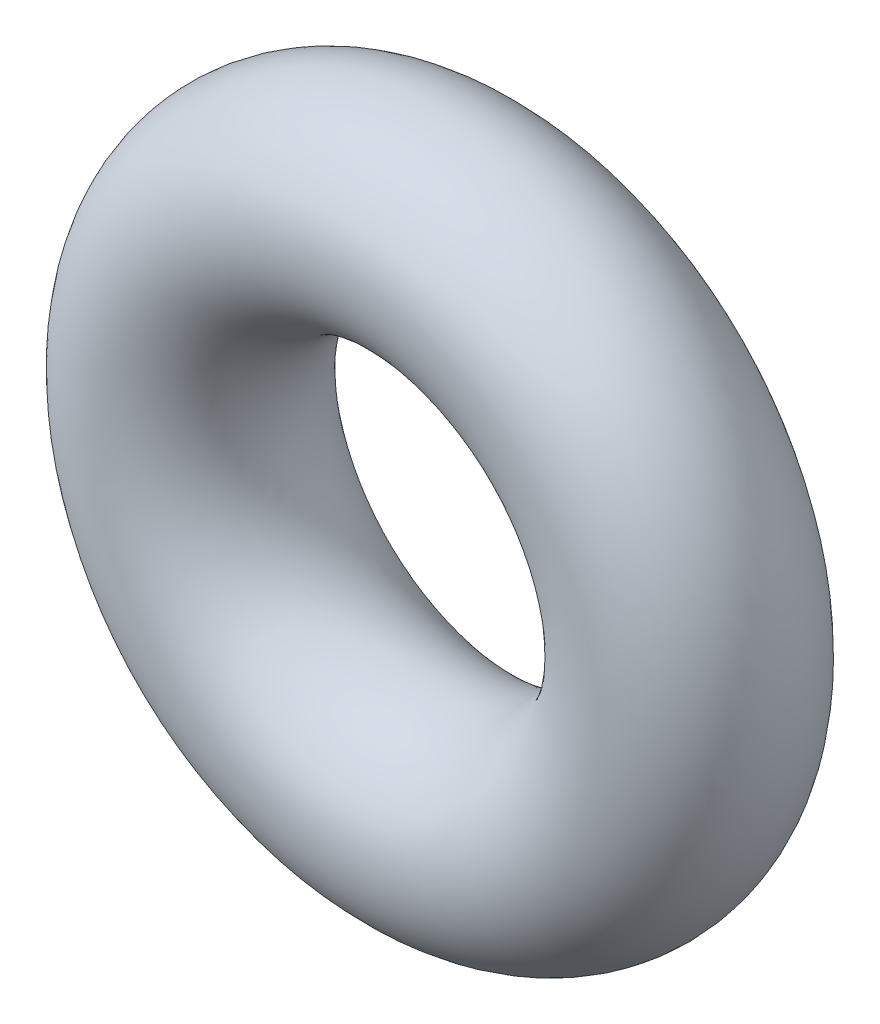
SolidWorks part; units mm, degrees
ref_plane "Front" through (0, 0, 0) normal (0, 0, 1) x (1, 0, 0)
ref_plane "Top" through (0, 0, 0) normal (0, 1, 0) x (1, 0, 0)
ref_plane "Right" through (0, 0, 0) normal (1, 0, 0) x (0, 0, -1)
sketch "Sketch1" plane through (0, 0, 0) normal (1, 0, 0) x (0, -1, 0)
  line L0 (0, -0.889) -> (0, 0.889) construction
  line L2 (-3.3668, 0) -> (3.3668, 0) construction
  line L3 (-1.2827, 0) -> (1.2827, 0) construction
  circle A0 centre (2.1717, 0) radius 0.889
  point P9 (1.2827, 0)
  point P10 (3.0607, 0)
  point P13 (2.1717, 0.889)
  point P14 (2.1717, -0.889)
  dimension "Width" = 1.778
  dimension "ID" = 2.5654
revolve "Revolve1" add sketch "Sketch1" angle 360 about L0
ref_axis "Axis1" through (0, 0, -0.9779) along (0, 0, 1)
